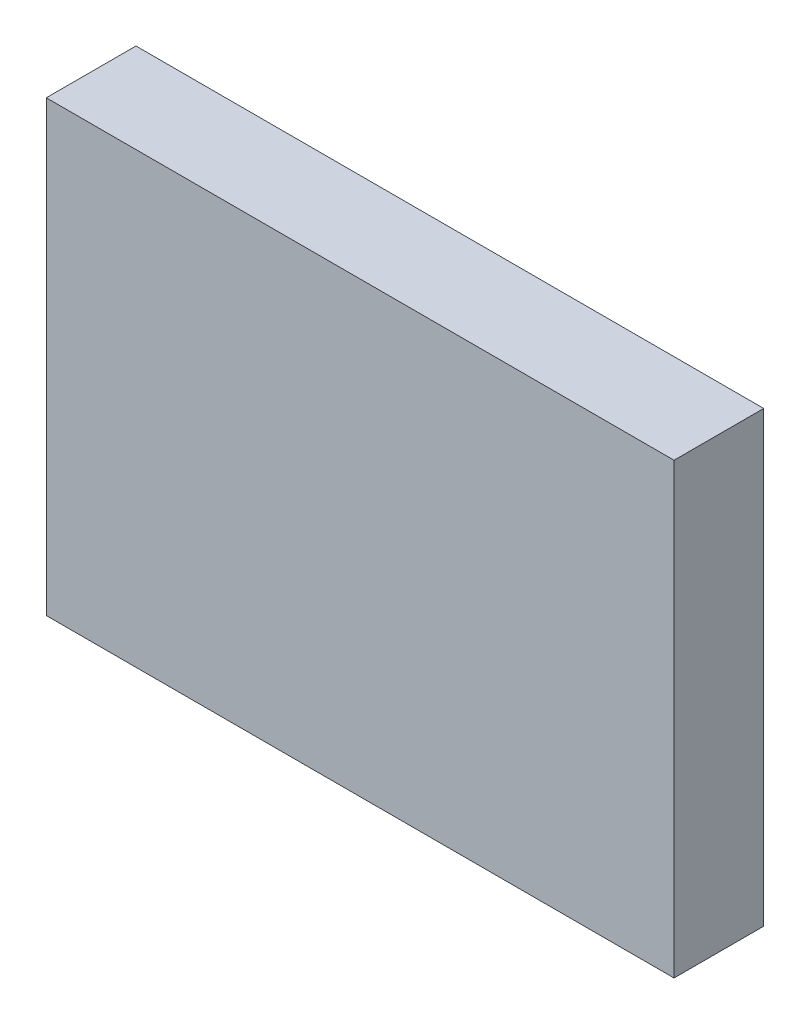
SolidWorks part; units mm, degrees
material "Polyurethane Foam Rigid"
ref_plane "X-Y Datum" through (0, 0, 0) normal (0, 0, 1) x (1, 0, 0)
ref_plane "X-Z Datum" through (0, 0, 0) normal (0, 1, 0) x (1, 0, 0)
ref_plane "Y-Z Datum" through (0, 0, 0) normal (1, 0, 0) x (0, 0, -1)
sketch "Sketch1" plane through (0, 0, 0) normal (0, 0, 1) x (1, 0, 0)
  line L1 (-88.9, -63.5) -> (88.9, -63.5)
  line L2 (-88.9, -63.5) -> (-88.9, 63.5)
  line L3 (-88.9, 63.5) -> (88.9, 63.5)
  line L4 (88.9, -63.5) -> (88.9, 63.5)
  line L5 (-88.9, -63.5) -> (88.9, 63.5) construction
  line L6 (-88.9, 63.5) -> (88.9, -63.5) construction
  point P0 (0, 0)
  dimension "D1" = 127
  dimension "D2" = 177.8
extrude "Boss-Extrude1" add sketch "Sketch1" along normal blind 25.4
